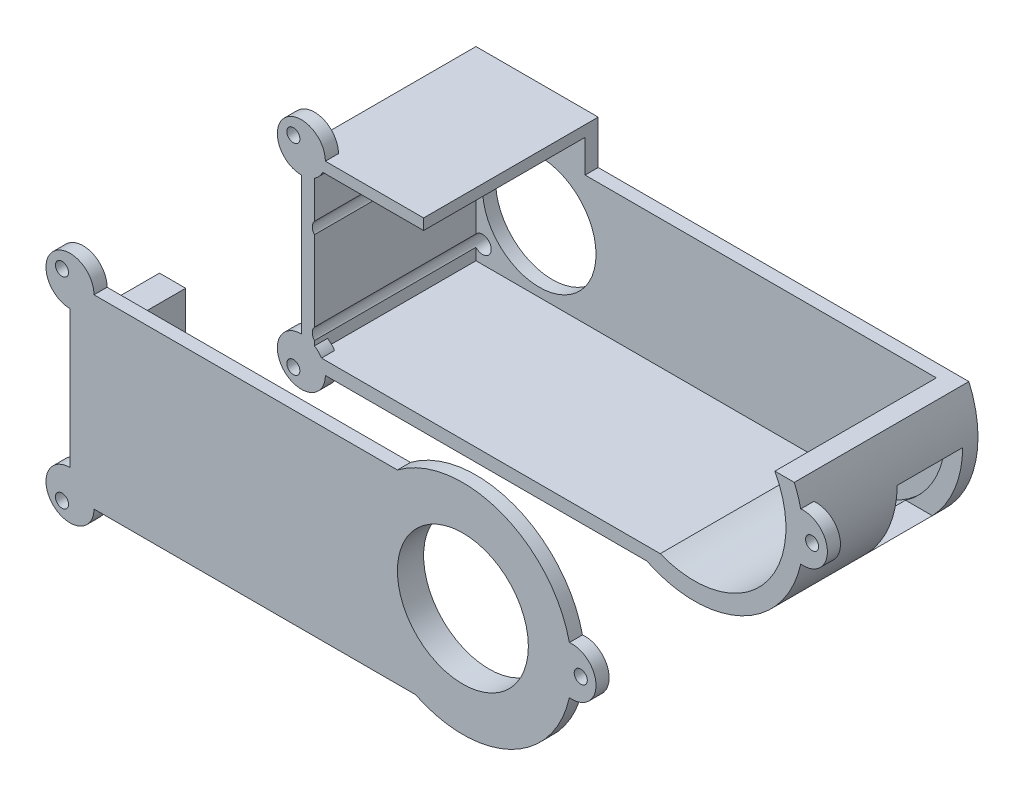
SolidWorks part; units mm, degrees
ref_plane "Front Plane" through (0, 0, 0) normal (0, 0, 1) x (1, 0, 0)
ref_plane "Top Plane" through (0, 0, 0) normal (0, 1, 0) x (1, 0, 0)
ref_plane "Right Plane" through (0, 0, 0) normal (1, 0, 0) x (0, 0, -1)
sketch "Sketch1" plane through (0, 0, 0) normal (0, 0, 1) x (1, 0, 0)
  line L1 (0, 0) -> (75, 0)
  line L2 (0, 0) -> (0, -42.5)
  line L3 (0, -42.5) -> (79.1028, -42.5)
  arc A0 (79.1028, -42.5) -> (75, 0) centre (90, -20) ccw
  dimension "D4" = 50
extrude "Boss-Extrude1" add sketch "Sketch1" along normal blind 40
sketch "Sketch2" plane through (0, 0, 40) normal (0, 0, 1) x (1, 0, 0)
  line L0 (0, 0) -> (0, -42.5) construction
  line L1 (3, -2.5) -> (78.3918, -2.5)
  line L2 (3, -2.5) -> (3, -39.5)
  line L3 (3, -39.5) -> (82.2058, -39.5)
  line L4 (75, 0) -> (0, 0) construction
  arc A0 (82.2058, -39.5) -> (78.3918, -2.5) centre (90, -20) ccw
  arc A1 (79.1028, -42.5) -> (75, 0) centre (90, -20) ccw construction
  dimension "D3" = 42
  dimension "D1" = 3
  dimension "D2" = 37
  dimension "D4" = 2.5
extrude "Cut-Extrude1" cut sketch "Sketch2" against normal blind 37
sketch "Sketch8" plane through (0, 0, 0) normal (0, 0, -1) x (-1, 0, 0)
  line L0 (-75, 0) -> (0, 0) construction
  line L1 (-66.3291, 0) -> (-28, 0)
  line L2 (-118, 0) -> (-118, -10)
  line L3 (-118, -10) -> (-28, -10)
  line L4 (-28, 0) -> (-28, -10)
  line L7 (-3, -2.5) -> (-3, -39.5) construction
  line L10 (-118, 0) -> (-118, 13.3555)
  line L11 (-118, 13.3555) -> (-66.3291, 13.3555)
  line L12 (-66.3291, 0) -> (-66.3291, 13.3555)
  dimension "D1" = 90
  dimension "D2" = 10
  dimension "D3" = 25
extrude "Cut-Extrude7" cut sketch "Sketch8" against normal up to next
sketch "Sketch4" plane through (0, 0, 3) normal (0, 0, 1) x (1, 0, 0)
  line L4 (3, -2.5) -> (3, -39.5) construction
  circle A0 centre (17.5, -24.5) radius 13
  dimension "D1" = 26
  dimension "D2" = 14.5
extrude "Cut-Extrude4" cut sketch "Sketch4" against normal blind 20
sketch "Sketch14" plane through (3, 0, 0) normal (1, 0, 0) x (0, 0, -1)
  line L1 (-3.5, -20.3065) -> (-18.5, -20.3065)
  line L2 (-3.5, -20.3065) -> (-3.5, -37.3065)
  line L3 (-3.5, -37.3065) -> (-18.5, -37.3065)
  line L4 (-18.5, -20.3065) -> (-18.5, -37.3065)
  line L5 (0, -45) -> (0, -10) construction
  dimension "D1" = 3.5
  dimension "D2" = 17
  dimension "D3" = 15
extrude "Cut-Extrude12" cut sketch "Sketch14" along normal through all
ref_plane "Plane11" through (0, -21.25, 0) normal (0, 1, 0) x (1, 0, 0)
sketch "Sketch9" plane through (0, 0, 40) normal (0, 0, 1) x (1, 0, 0)
  line L1 (0, -42.5) -> (79.1028, -42.5) construction
  circle A0 centre (3.5, -16.5) radius 1.5
  circle A1 centre (96.5, -11) radius 1.5
  circle A2 centre (96.5, -37.5) radius 1.5
  circle A3 centre (3.5, -37.5) radius 1.5
  circle A5 centre (17.5, -24.5) radius 13 construction
  point P6 (0, 0)
  point P7 (0, 0)
  point P8 (0, 0)
  dimension "D1" = 26.5
  dimension "D2" = 5
  dimension "D3" = 79
  dimension "D4" = 93
  dimension "D5" = 21
extrude "Cut-Extrude8" [suppressed] cut sketch "Sketch9" against normal blind 10
ref_plane "Plane12" through (0, 0, 90) normal (0, 0, 1) x (1, 0, 0)
sketch "Sketch15" plane through (0, 0, 90) normal (0, 0, 1) x (1, 0, 0)
  line L0 (0, -42.5) -> (79.1028, -42.5) construction
  line L1 (0, 0) -> (75, 0)
  line L2 (0, 0) -> (0, -42.5)
  line L3 (0, -42.5) -> (79.1028, -42.5)
  arc A0 (79.1028, -42.5) -> (75, 0) centre (90, -20) ccw
  arc A1 (79.1028, -42.5) -> (112.9129, -10) centre (90, -20) ccw construction
  dimension "D1" = 50
extrude "Boss-Extrude2" add sketch "Sketch15" along normal blind 3 separate body
sketch "Sketch17" plane through (0, 0, 93) normal (0, 0, 1) x (1, 0, 0)
  line L1 (3.5, -3) -> (78.3656, -3)
  line L2 (3.5, -3) -> (3.5, -39)
  line L3 (3.5, -39) -> (82.0401, -39)
  line L8 (75, 0) -> (0, 0) construction
  line L9 (0, -42.5) -> (79.1028, -42.5) construction
  line L11 (0, 0) -> (0, -42.5) construction
  arc A0 (82.0401, -39) -> (78.3656, -3) centre (90, -20) ccw
  arc A2 (79.1028, -42.5) -> (75, 0) centre (90, -20) ccw construction
  dimension "D3" = 41.2
  dimension "D1" = 3.5
  dimension "D2" = 3.5
  dimension "D4" = 3
extrude "Boss-Extrude3" add sketch "Sketch17" against normal blind 6
sketch "Sketch18" plane through (3.5, 0, 0) normal (-1, 0, 0) x (0, 0, 1)
  line L0 (87, -3) -> (87, -39) construction
  line L1 (87, -5.1981) -> (76, -5.1981)
  line L2 (87, -5.1981) -> (87, -34.585)
  line L3 (87, -34.585) -> (76, -34.585)
  line L4 (76, -5.1981) -> (76, -34.585)
  dimension "D1" = 11
extrude "Boss-Extrude4" add sketch "Sketch18" against normal blind 6
sketch "Sketch19" plane through (0, 0, 93) normal (0, 0, 1) x (1, 0, 0)
  circle A0 centre (90, -20) radius 15
  arc A1 (79.1028, -42.5) -> (75, 0) centre (90, -20) ccw construction
  dimension "D1" = 30
extrude "Cut-Extrude13" cut sketch "Sketch19" against normal up to surface (6 mm away) up to face at (27.962, -20.0593, 87)
sketch "Sketch20" plane through (0, 0, 93) normal (0, 0, 1) x (1, 0, 0)
  line L0 (0, -42.5) -> (79.1028, -42.5) construction
  circle A0 centre (0, 0) radius 5.5
  circle A1 centre (0, -42.5) radius 5.5
  circle A2 centre (115, -20) radius 5.5
  arc A3 (79.1028, -42.5) -> (75, 0) centre (90, -20) ccw construction
  circle A4 centre (-1.8367, 1.5) radius 1.5
  circle A5 centre (-1.8367, -44.5) radius 1.5
  circle A6 centre (117, -20) radius 1.5
  dimension "D1" = 11
  dimension "D2" = 11
  dimension "D3" = 11
  dimension "D4" = 3
  dimension "D5" = 3
  dimension "D6" = 3
  dimension "D7" = 2
  dimension "D8" = 46
  dimension "D9" = 2
extrude "Boss-Extrude5" add sketch "Sketch20" against normal up to surface (3 mm away) up to face at (49.4241, -20.2271, 90)
sketch "Sketch21" plane through (0, 0, 40) normal (0, 0, 1) x (1, 0, 0)
  circle A0 centre (0, 0) radius 5.5
  circle A1 centre (0, -42.5) radius 5.5
  arc A2 (0, -37) -> (5.5, -42.5) centre (0, -42.5) ccw construction
  circle A3 centre (115, -20) radius 5.5
  arc A4 (114.395, -25.4666) -> (114.395, -14.5334) centre (115, -20) ccw construction
  circle A5 centre (-1.8367, 1.5) radius 1.5
  circle A6 centre (-1.8367, -44.5) radius 1.5
  circle A7 centre (117, -20) radius 1.5
extrude "Boss-Extrude6" add sketch "Sketch21" against normal blind 3
sketch "Sketch22" plane through (0, 0, 3) normal (0, 0, 1) x (1, 0, 0)
  circle A0 centre (90, -20) radius 21
  arc A1 (82.2058, -39.5) -> (108.4662, -10) centre (90, -20) ccw construction
extrude "Cut-Extrude14" cut sketch "Sketch22" along normal blind 66
sketch "Sketch23" plane through (0, 0, 0) normal (0, 0, -1) x (-1, 0, 0)
  circle A0 centre (-4.5, -35.5) radius 2
  circle A1 centre (-4.5, -14.5) radius 2
  circle A2 centre (-17.5, -24.5) radius 13 construction
  point P6 (0, 0)
  dimension "D2" = 4
  dimension "D3" = 4
  dimension "D1" = 13
  dimension "D4" = 10
  dimension "D5" = 11
extrude "Cut-Extrude15" cut sketch "Sketch23" against normal up to surface (40 mm away) up to face at (43.8507, -20.7343, 40)
equation "\"D2@Sketch20\"=\"D1@Sketch20\""
equation "\"D3@Sketch20\"=\"D1@Sketch20\""
equation "\"D5@Sketch20\"=\"D4@Sketch20\""
equation "\"D6@Sketch20\"=\"D4@Sketch20\""
equation "\"D3@Sketch23\"=\"D2@Sketch23\""
